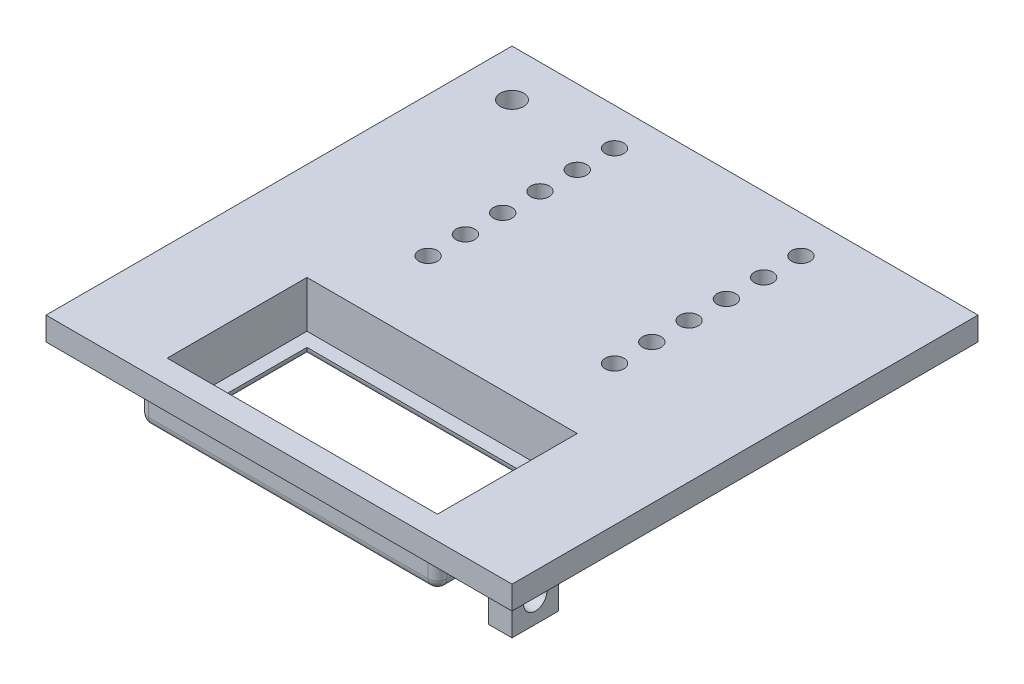
SolidWorks part; units mm, degrees
ref_plane "Front Plane" through (0, 0, 0) normal (0, 0, 1) x (1, 0, 0)
ref_plane "Top Plane" through (0, 0, 0) normal (0, 1, 0) x (1, 0, 0)
ref_plane "Right Plane" through (0, 0, 0) normal (1, 0, 0) x (0, 0, -1)
sketch "Sketch1" plane through (0, 0, 0) normal (0, 1, 0) x (1, 0, 0)
  line L0 (23.5385, 23.001) -> (23.5385, -76.999) construction
  line L1 (-26.4615, 23.001) -> (73.5385, 23.001)
  line L2 (-26.4615, 23.001) -> (-26.4615, -76.999)
  line L3 (-26.4615, -76.999) -> (73.5385, -76.999)
  line L4 (73.5385, 23.001) -> (73.5385, -76.999)
  line L10 (-5.4615, -41.999) -> (52.5385, -41.999)
  line L11 (-5.4615, -41.999) -> (-5.4615, -71.999)
  line L12 (-5.4615, -71.999) -> (52.5385, -71.999)
  line L13 (52.5385, -41.999) -> (52.5385, -71.999)
  circle A0 centre (3.5385, 15.001) radius 2
  circle A6 centre (3.5385, 7.001) radius 2
  circle A7 centre (3.5385, -0.999) radius 2
  circle A8 centre (3.5385, -8.999) radius 2
  circle A9 centre (3.5385, -16.999) radius 2
  circle A10 centre (3.5385, -24.999) radius 2
  circle A11 centre (43.5385, -24.999) radius 2
  circle A12 centre (43.5385, -16.999) radius 2
  circle A13 centre (43.5385, -8.999) radius 2
  circle A14 centre (43.5385, -0.999) radius 2
  circle A15 centre (43.5385, 7.001) radius 2
  circle A16 centre (43.5385, 15.001) radius 2
  point P34 (23.5385, -71.999)
  dimension "D1" = 4
  dimension "D2" = 6
  dimension "D3" = 30
  dimension "D4" = 8
  dimension "D5" = 30
  dimension "D6" = 100
  dimension "D7" = 100
  dimension "D8" = 58
  dimension "D9" = 5
  dimension "D10" = 8
extrude "Boss-Extrude1" add sketch "Sketch1" along normal blind 5
sketch "Sketch2" plane through (0, 0, 0) normal (0, -1, 0) x (1, 0, 0)
  line L1 (-5.4615, 71.999) -> (52.5385, 71.999)
  line L2 (-5.4615, 71.999) -> (-5.4615, 41.999)
  line L3 (-5.4615, 41.999) -> (52.5385, 41.999)
  line L4 (52.5385, 71.999) -> (52.5385, 41.999)
  line L5 (-8.4615, 74.999) -> (55.5385, 74.999)
  line L6 (-8.4615, 74.999) -> (-8.4615, 38.999)
  line L7 (-8.4615, 38.999) -> (55.5385, 38.999)
  line L8 (55.5385, 74.999) -> (55.5385, 38.999)
  dimension "D1" = 3
  dimension "D2" = 3
  dimension "D3" = 3
  dimension "D4" = 3
extrude "Boss-Extrude2" add sketch "Sketch2" along normal blind 5
sketch "Sketch3" plane through (0, -5, 0) normal (0, -1, 0) x (1, 0, 0)
  line L1 (-8.4615, 74.999) -> (55.5385, 74.999)
  line L2 (-8.4615, 74.999) -> (-8.4615, 38.999)
  line L3 (-8.4615, 38.999) -> (55.5385, 38.999)
  line L4 (55.5385, 74.999) -> (55.5385, 38.999)
  line L5 (-2.4615, 68.999) -> (49.5385, 68.999)
  line L6 (-2.4615, 68.999) -> (-2.4615, 44.999)
  line L7 (-2.4615, 44.999) -> (49.5385, 44.999)
  line L8 (49.5385, 68.999) -> (49.5385, 44.999)
  dimension "D1" = 6
  dimension "D2" = 6
  dimension "D3" = 6
  dimension "D4" = 6
extrude "Boss-Extrude3" add sketch "Sketch3" along normal blind 2
fillet "Fillet2" radius 2 16 edges at (49.5385, -7, 56.999) (23.5385, -7, 68.999) (-2.4615, -7, 56.999) (23.5385, -7, 44.999) (23.5385, -7, 74.999) (55.5385, -7, 56.999) (23.5385, -7, 38.999) (-8.4615, -7, 56.999) (-8.4615, -3.5, 38.999) (55.5385, -3.5, 38.999) (55.5385, -3.5, 74.999) (-8.4615, -3.5, 74.999) (-8.4615, 0, 56.999) (23.5385, 0, 74.999) (55.5385, 0, 56.999) (23.5385, 0, 38.999)
sketch "Sketch5" plane through (0, 0, 0) normal (0, -1, 0) x (1, 0, 0)
  line L0 (73.5385, 76.999) -> (73.5385, -23.001) construction
  line L1 (68.5385, 61.999) -> (63.5385, 61.999)
  line L2 (68.5385, 61.999) -> (68.5385, 71.999)
  line L3 (68.5385, 71.999) -> (63.5385, 71.999)
  line L4 (63.5385, 61.999) -> (63.5385, 71.999)
  line L7 (53.5385, 76.999) -> (73.5385, 76.999) construction
  dimension "D1" = 5
  dimension "D2" = 10
  dimension "D3" = 5
  dimension "D4" = 5
extrude "Boss-Extrude4" add sketch "Sketch5" along normal blind 10
sketch "Sketch6" plane through (68.5385, 0, 0) normal (1, 0, 0) x (0, 0, -1)
  line L0 (-61.999, -10) -> (-61.999, 0) construction
  line L1 (-61.999, -10) -> (-71.999, -10) construction
  circle A0 centre (-66.999, -5) radius 2.5
  point P4 (-61.999, -5)
  point P7 (-66.999, -10)
  dimension "D1" = 5
extrude "Cut-Extrude2" cut sketch "Sketch6" against normal blind 8
sketch "Sketch7" plane through (0, 0, 0) normal (0, -1, 0) x (1, 0, 0)
  line L0 (73.5385, -23.001) -> (-26.4615, -23.001) construction
  line L1 (-26.4615, -23.001) -> (-26.4615, 76.999) construction
  circle A0 centre (-16.4615, -13.001) radius 2.5
  dimension "D1" = 5
  dimension "D3" = 10
  dimension "D2" = 10
extrude "Cut-Extrude3" cut sketch "Sketch7" against normal blind 8
